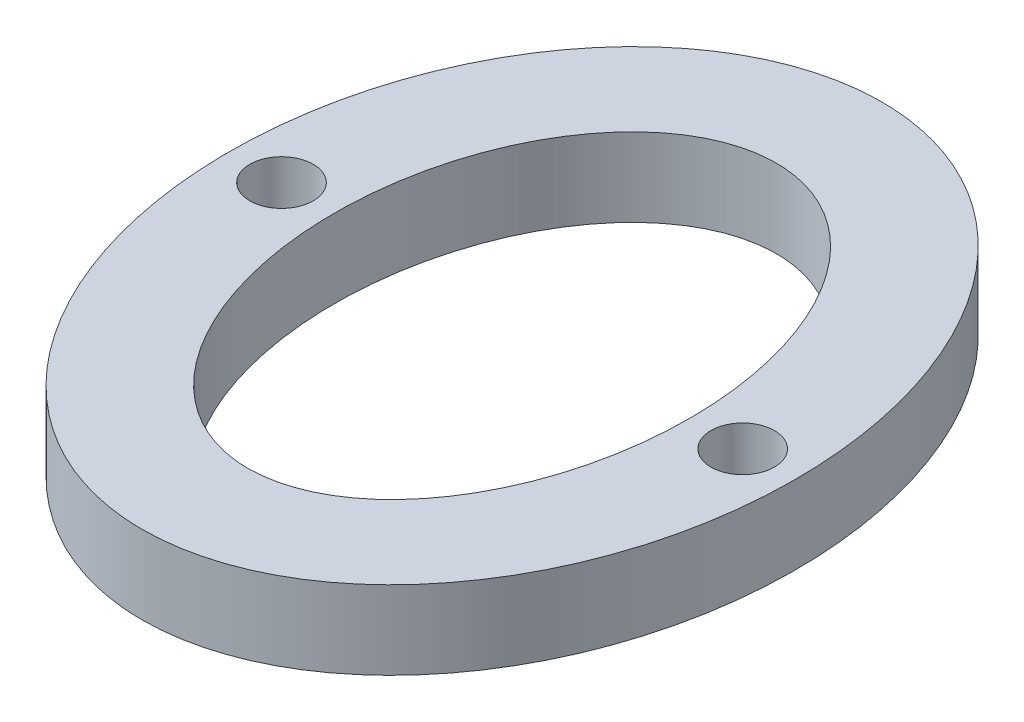
SolidWorks part; units mm, degrees
ref_plane "Front Plane" through (0, 0, 0) normal (0, 0, 1) x (1, 0, 0)
ref_plane "Top Plane" through (0, 0, 0) normal (0, 1, 0) x (1, 0, 0)
ref_plane "Right Plane" through (0, 0, 0) normal (1, 0, 0) x (0, 0, -1)
sketch "Sketch1" plane through (0, 0, 0) normal (0, 1, 0) x (1, 0, 0)
  line L0 (-27.7, 0) -> (0, 0) construction
  line L1 (-13.85, 15.875) -> (-13.85, 22.225) construction
  circle A0 centre (0, 0) radius 1.905
  circle A1 centre (-27.7, 0) radius 1.905
  circle A2 centre (-27.7, 0) radius 3.175
  circle A3 centre (0, 0) radius 3.175
  ellipse E0 centre (-13.85, 0) end of major axis (-13.85, -22.225) minor radius 17.025
  ellipse E1 centre (-13.85, 0) end of major axis (-13.85, -15.875) minor radius 10.675
  point P11 (-13.85, 27.8102)
  dimension "D1" = 3.81
  dimension "D3" = 6.35
  dimension "D4" = 1.27
  dimension "D2" = 27.7
  dimension "D5" = 6.35
  dimension "D6" = 44.45
extrude "Boss-Extrude1" add sketch "Sketch1" along normal blind 4.7117 contours E0 A2 | E0 A3 | E0 | A3 A0 | E0 A3 | E0 | E0 A2 | A2 A1 region at (-27.7, 0, 3.0852) region at (-22.4278, 0, 10.3217) region at (-27.7, 0, -3.5816) region at (0, 0, -3.0852)
